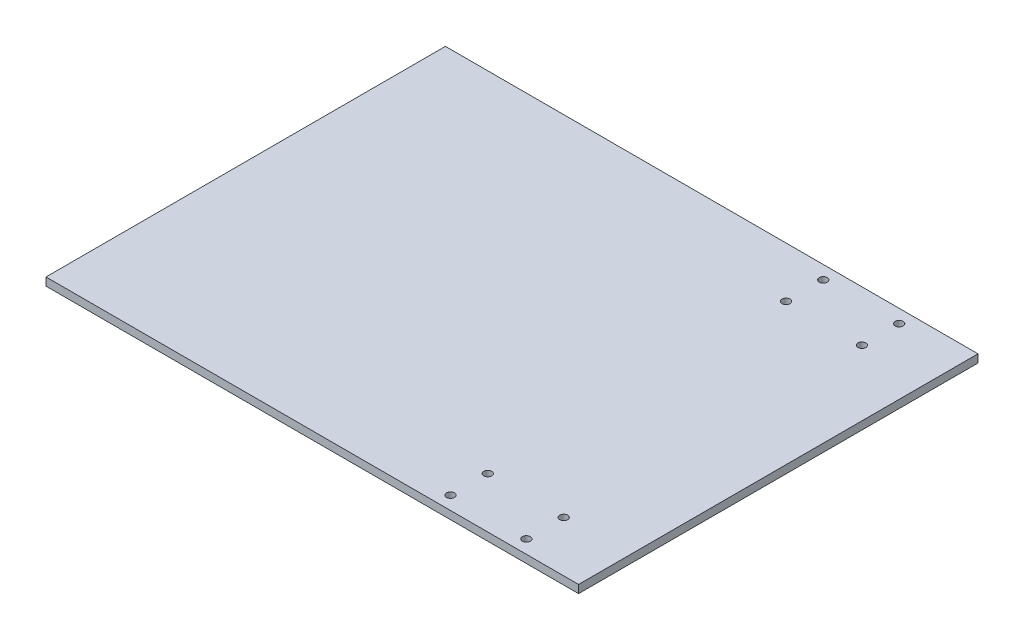
SolidWorks part; units mm, degrees
ref_plane "Front Plane" through (0, 0, 0) normal (0, 0, 1) x (1, 0, 0)
ref_plane "Top Plane" through (0, 0, 0) normal (0, 1, 0) x (1, 0, 0)
ref_plane "Right Plane" through (0, 0, 0) normal (1, 0, 0) x (0, 0, -1)
sketch "Sketch2" plane through (0, 0, 0) normal (0, 1, 0) x (1, 0, 0)
  line L1 (0, 0) -> (200, 0)
  line L2 (0, 0) -> (0, 150)
  line L3 (0, 150) -> (200, 150)
  line L4 (200, 0) -> (200, 150)
  dimension "D1" = 200
  dimension "D2" = 150
extrude "Boss-Extrude1" add sketch "Sketch2" along normal blind 3
sketch "Sketch3" plane through (0, 3, 0) normal (0, 1, 0) x (1, 0, 0)
  line L0 (200, 0) -> (200, 150) construction
  line L2 (100, 150) -> (100, 0) construction
  line L3 (200, 150) -> (0, 150) construction
  line L4 (0, 0) -> (200, 0) construction
  line L5 (0, 75) -> (200, 75) construction
  line L6 (0, 150) -> (0, 0) construction
  line L7 (200, 0) -> (200, 150) construction
  line L8 (200, 150) -> (0, 150) construction
  circle A1 centre (175.4, 145) radius 1.5
  circle A2 centre (146.9, 145) radius 1.5
  circle A3 centre (175.4, 131) radius 1.5
  circle A4 centre (146.9, 131) radius 1.5
  circle A5 centre (175.4, 19) radius 1.5
  circle A6 centre (175.4, 5) radius 1.5
  circle A7 centre (146.9, 5) radius 1.5
  circle A8 centre (146.9, 19) radius 1.5
  dimension "D1" = 3
  dimension "D2" = 3
  dimension "D3" = 3
  dimension "D4" = 3
  dimension "D5" = 5
  dimension "D6" = 24.6
  dimension "D7" = 14
  dimension "D8" = 24.6
  dimension "D9" = 28.5
  dimension "D10" = 5
  dimension "D11" = 14
  dimension "D12" = 28.5
extrude "Cut-Extrude1" cut sketch "Sketch3" against normal through all
